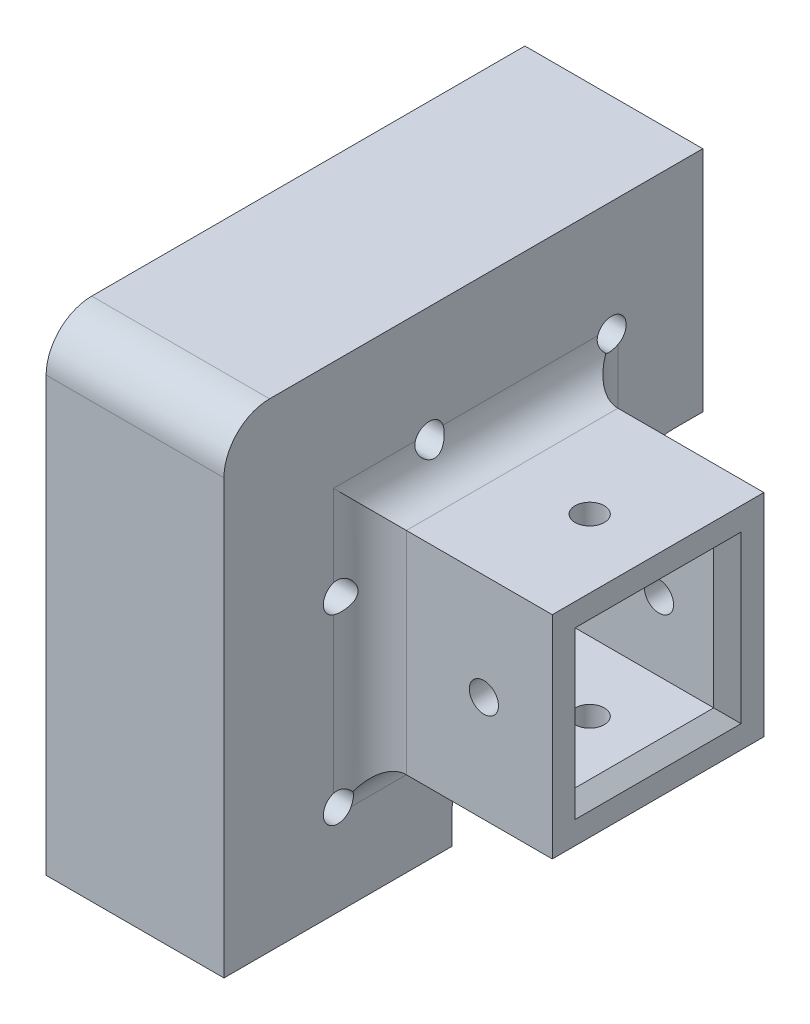
SolidWorks part; units mm, degrees
material "PLA"
ref_plane "前视基准面" through (0, 0, 0) normal (0, 0, 1) x (1, 0, 0)
ref_plane "上视基准面" through (0, 0, 0) normal (0, 1, 0) x (1, 0, 0)
ref_plane "右视基准面" through (0, 0, 0) normal (1, 0, 0) x (0, 0, -1)
sketch "草图1" plane through (0, 0, 0) normal (1, 0, 0) x (0, 0, -1)
  line L0 (0, 0) -> (40, 0) construction
  line L1 (0, 0) -> (0, -40) construction
  line L2 (12.5, -30.7) -> (30.7, -30.7)
  line L3 (7.5, -7.5) -> (22.7, -7.5)
  line L4 (7.5, -7.5) -> (7.5, -22.7)
  line L5 (7.5, -22.7) -> (22.7, -22.7)
  line L6 (22.7, -7.5) -> (22.7, -22.7)
  line L7 (30.7, -12.5) -> (30.7, -30.7)
  line L8 (7.5, -7.5) -> (40, -7.5) construction
  line L9 (12.5, -40) -> (-12.5, -40)
  line L10 (-12.5, 12.5) -> (-12.5, -40)
  line L11 (-12.5, 12.5) -> (40, 12.5)
  line L12 (40, 12.5) -> (40, -12.5)
  line L13 (7.5, -7.5) -> (7.5, -40) construction
  line L14 (30.7, -7.5) -> (30.7, -30.7) construction
  line L15 (7.5, -30.7) -> (30.7, -30.7) construction
  line L16 (-7.5, 7.5) -> (-7.5, -40) construction
  line L17 (-7.5, 7.5) -> (40, 7.5) construction
  line L18 (-7.5, 7.5) -> (-7.5, -40) construction
  line L19 (-7.5, 7.5) -> (40, 7.5) construction
  line L20 (12.5, -30.7) -> (12.5, -40)
  line L21 (30.7, -12.5) -> (40, -12.5)
  line L22 (12.5, -12.5) -> (12.5, -40) construction
  line L23 (12.5, -12.5) -> (40, -12.5) construction
  line L24 (7.5, -7.5) -> (40, -7.5) construction
  line L25 (7.5, -7.5) -> (7.5, -40) construction
  line L26 (0, 0) -> (0, -40) construction
  line L27 (0, 0) -> (40, 0) construction
  line L28 (-7.5, 7.5) -> (7.5, -7.5) construction
  circle A0 centre (10, 0) radius 1.6
  circle A2 centre (30, 0) radius 1.6
  circle A3 centre (0, -30) radius 1.6
  circle A5 centre (0, -10) radius 1.6
  dimension "D10" = 10
  dimension "D11" = 3.2
  dimension "D12" = 10
  dimension "D1" = 15.2
  dimension "D2" = 7.5
  dimension "D3" = 7.5
  dimension "D5" = 7.5
  dimension "D9" = 40
  dimension "D4" = 8
  dimension "D6" = 5
  dimension "D7" = 7.5
  dimension "D8" = 5
extrude "凸台-拉伸1" add sketch "草图1" along normal blind 19.5
sketch "草图2" plane through (0, 0, 0) normal (-1, 0, 0) x (0, 0, 1)
  line L0 (0, 0) -> (0, -40) construction
  line L1 (12.5, -40) -> (-12.5, -40) construction
  line L2 (0, 0) -> (-40, 0) construction
  line L3 (-40, -12.5) -> (-40, 12.5) construction
  line L4 (7.5, 7.5) -> (7.5, -40)
  line L5 (7.5, 7.5) -> (-40, 7.5)
  line L6 (-7.5, -7.5) -> (-40, -7.5)
  line L7 (-7.5, -7.5) -> (-7.5, -40)
  line L8 (-40, 7.5) -> (-40, -7.5)
  line L9 (7.5, -40) -> (-7.5, -40)
  dimension "D1" = 7.5
  dimension "D2" = 7.5
extrude "切除-拉伸1" cut sketch "草图2" against normal blind 14.5
sketch "草图3" plane through (19.5, 0, 0) normal (1, 0, 0) x (0, 0, -1)
  line L0 (7.5, -22.7) -> (22.7, -22.7) construction
  line L1 (7.5, -7.5) -> (7.5, -22.7) construction
  line L2 (22.7, -7.5) -> (7.5, -7.5) construction
  line L3 (22.7, -22.7) -> (22.7, -7.5) construction
  line L4 (7.5, -22.7) -> (22.7, -22.7)
  line L5 (7.5, -7.5) -> (7.5, -22.7)
  line L6 (22.7, -7.5) -> (7.5, -7.5)
  line L7 (22.7, -22.7) -> (22.7, -7.5)
  line L8 (3.5, -26.7) -> (26.7, -26.7)
  line L9 (26.7, -26.7) -> (26.7, -3.5)
  line L10 (26.7, -3.5) -> (3.5, -3.5)
  line L11 (3.5, -3.5) -> (3.5, -26.7)
  dimension "D1" = 4
extrude "凸台-拉伸2" add sketch "草图3" along normal blind 20
fillet "圆角1" radius 4 4 edges at (19.5, -26.7, -15.1) (19.5, -15.1, -26.7) (19.5, -3.5, -15.1) (19.5, -15.1, -3.5)
fillet "圆角2" radius 6 3 edges at (9.75, -30.7, -12.5) (9.75, -12.5, -30.7) (9.75, -30.7, -30.7)
chamfer "倒角1" distance 1.5 angle 45 4 edges at (39.5, -7.5, -15.1) (39.5, -15.1, -7.5) (39.5, -22.7, -15.1) (39.5, -15.1, -22.7)
chamfer "倒角2" distance 1 angle 45 4 edges at (0, -7.5, -31.35) (0, -31.35, -7.5) (0, 7.5, -16.25) (0, -16.25, 7.5)
sketch "草图4" plane through (0, 0, -3.5) normal (0, 0, 1) x (1, 0, 0)
  line L0 (39.5, -3.5) -> (39.5, -26.7) construction
  circle A0 centre (32, -15.1) radius 1.6
  point P5 (39.5, -15.1)
  dimension "D1" = 3.2
  dimension "D2" = 7.5
extrude "切除-拉伸2" cut sketch "草图4" against normal through all
sketch "草图5" plane through (0, -3.5, 0) normal (0, 1, 0) x (1, 0, 0)
  line L0 (39.5, 26.7) -> (39.5, 3.5) construction
  circle A0 centre (32, 15.1) radius 1.6
  point P5 (39.5, 15.1)
  dimension "D1" = 3.2
  dimension "D2" = 7.5
extrude "切除-拉伸3" cut sketch "草图5" against normal through all
fillet "圆角3" radius 5 1 edges at (9.75, 12.5, 12.5)
